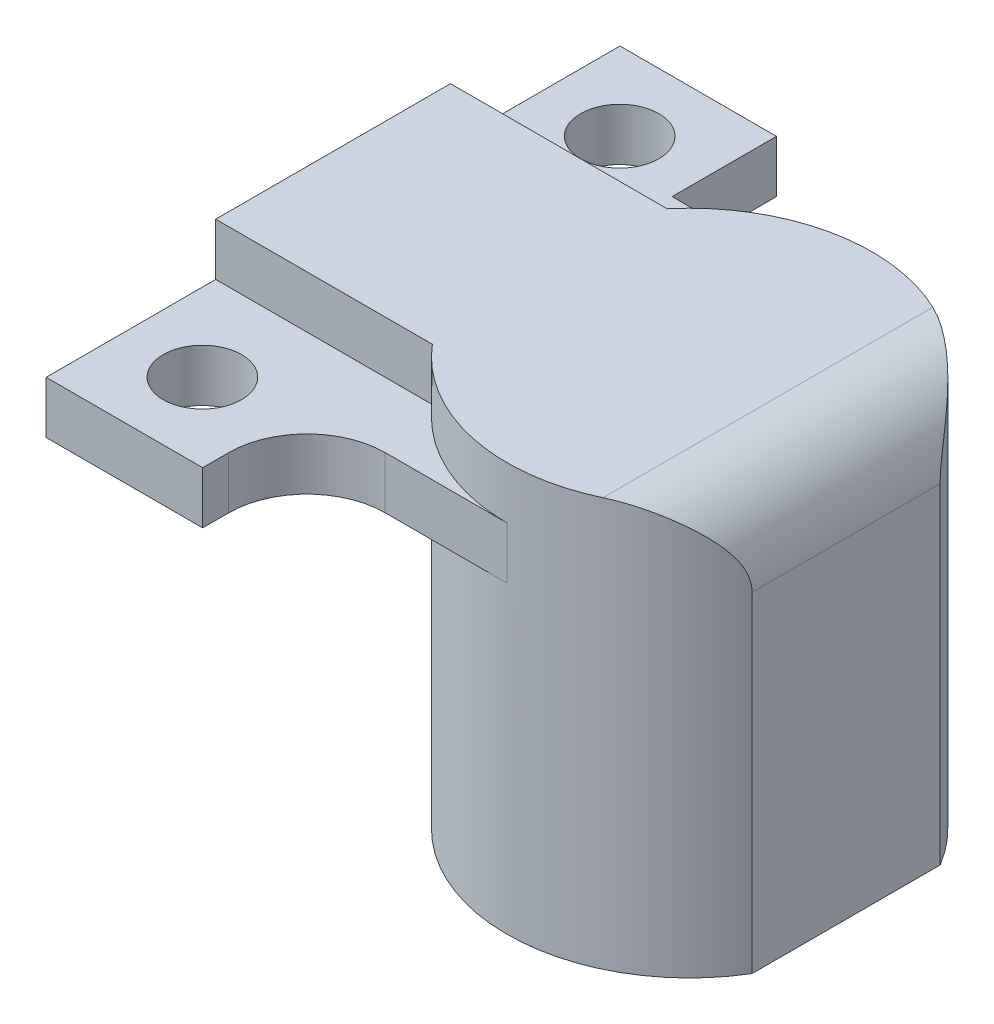
SolidWorks part; units mm, degrees
material "Copper"
ref_plane "Front Plane" through (0, 0, 0) normal (0, 0, 1) x (1, 0, 0)
ref_plane "Top Plane" through (0, 0, 0) normal (0, 1, 0) x (1, 0, 0)
ref_plane "Right Plane" through (0, 0, 0) normal (1, 0, 0) x (0, 0, -1)
sketch "Sketch1" plane through (0, 0, 0) normal (0, 1, 0) x (1, 0, 0)
  circle A0 centre (0, 0) radius 5.2
  circle A1 centre (0, 0) radius 7
  dimension "D1" = 10.4
  dimension "D2" = 14
extrude "Boss-Extrude1" add sketch "Sketch1" along normal blind 15.66
sketch "Sketch2" plane through (0, 15.66, 0) normal (0, 1, 0) x (1, 0, 0)
  line L0 (0, 0) -> (-6.5789, 0) construction
  line L1 (0, 5.2) -> (0, 7)
  line L2 (-13.67, -7) -> (0, -7)
  line L3 (-13.67, -7) -> (-13.67, 7)
  line L4 (-13.67, 7) -> (0, 7)
  line L5 (0, -7) -> (0, -5.2)
  line L6 (-13.67, -7) -> (0, 7) construction
  line L7 (-13.67, 7) -> (0, -7) construction
  line L8 (-7.67, 7) -> (-7.67, 11)
  line L9 (-13.67, -7) -> (-7.67, -7)
  line L10 (-13.67, -7) -> (-13.67, -11)
  line L11 (-13.67, -11) -> (-7.67, -11)
  line L12 (-7.67, -7) -> (-7.67, -11)
  line L13 (-13.67, 11) -> (-7.67, 11)
  line L14 (-13.67, 7) -> (-13.67, 11)
  line L15 (-13.67, 7) -> (-7.67, 7)
  circle A0 centre (0, 0) radius 7 construction
  circle A1 centre (0, 0) radius 5.2 construction
  arc A2 (0, 5.2) -> (0, -5.2) centre (0, 0) ccw
  point P3 (-6.835, 0)
  circle M6 centre (0, 0) radius 7
  dimension "D1" = 4
  dimension "D2" = 13.67
  dimension "D3" = 6
extrude "Boss-Extrude2" add sketch "Sketch2" against normal blind 4 contours L12 L2 L10 L11 | L4 L3 L2 M6 | L15 L8 L13 L14 region at (-9.4345, 15.66, 0) region at (-10.67, 15.66, 9)
extrude "Cut-Extrude2" cut sketch "Sketch2<3>" against normal blind 2 contours L4 L3 L2 M6 | L14 L4 L8 L13 | L12 L2 L10 L11 region at (-9.4345, 15.66, 0) region at (-10.67, 15.66, -9) region at (-10.67, 15.66, 9)
sketch "Sketch2<3>" plane through (0, 15.66, 0) normal (0, 1, 0) x (1, 0, 0) same geometry as "Sketch2"
sketch "Sketch4" plane through (0, 11.66, 0) normal (0, -1, 0) x (1, 0, 0)
  line L0 (-13.67, 8) -> (-7.899, 8) construction
  line L2 (-13.67, -11) -> (-13.67, 11) construction
  line L3 (0, 0) -> (-21.2142, 0) construction
  line L4 (-13.67, 11) -> (-7.67, 11) construction
  circle A0 centre (-10.68, 8) radius 1.5
  circle A1 centre (-10.68, -8) radius 1.5
  dimension "D1" = 3
  dimension "D2" = 2.99
  dimension "D3" = 3
extrude "Cut-Extrude1" cut sketch "Sketch4" against normal blind 10 contours A1 | A0 region at (-10.68, 11.66, -8)
fillet "Fillet7" radius 3 1 edges at (-7.67, 12.66, 7) type face fillet first side face at (-3.835, 12.66, 7) second side face at (-7.67, 12.66, 9) tangent propagation no
sketch "Sketch5" plane through (0, 15.66, 0) normal (0, 1, 0) x (1, 0, 0)
  circle A0 centre (0, 0) radius 5.2 construction
  circle A1 centre (0, 0) radius 5.2
extrude "Boss-Extrude3" add sketch "Sketch5" against normal blind 1
sketch "Sketch6" plane through (0, 0, 0) normal (0, -1, 0) x (1, 0, 0)
  line L0 (6, -3.6056) -> (6, 3.6056)
  circle A0 centre (0, 0) radius 7 construction
  arc A3 (6, -3.6056) -> (6, 3.6056) centre (0, 0) ccw
  point P5 (7, 0)
  dimension "D1" = 1
extrude "Cut-Extrude3" cut sketch "Sketch6" along direction (0, 1, 0) on the side against the normal up to next
fillet "Fillet8" radius 3 1 edges at (6, 15.66, 0) type face fillet first side face at (6, 7.83, 0) second side face at (-0.5, 15.66, 0) tangent propagation no
sketch "Sketch7" plane through (0, 13.66, 0) normal (0, 1, 0) x (1, 0, 0)
  line L1 (-13.67, -11) -> (-13.67, 11) construction
  line L2 (-13.67, 4.5) -> (-13.67, -4.5)
  line L3 (-13.67, -4.5) -> (-5.3619, -4.5)
  line L4 (-13.67, 4.5) -> (-5.3619, 4.5)
  arc A0 (3, 6.3246) -> (3, -6.3246) centre (0, 0) ccw construction
  arc A1 (-5.3619, 4.5) -> (-5.3619, -4.5) centre (0, 0) ccw
extrude "Boss-Extrude4" add sketch "Sketch7" along normal blind 2
